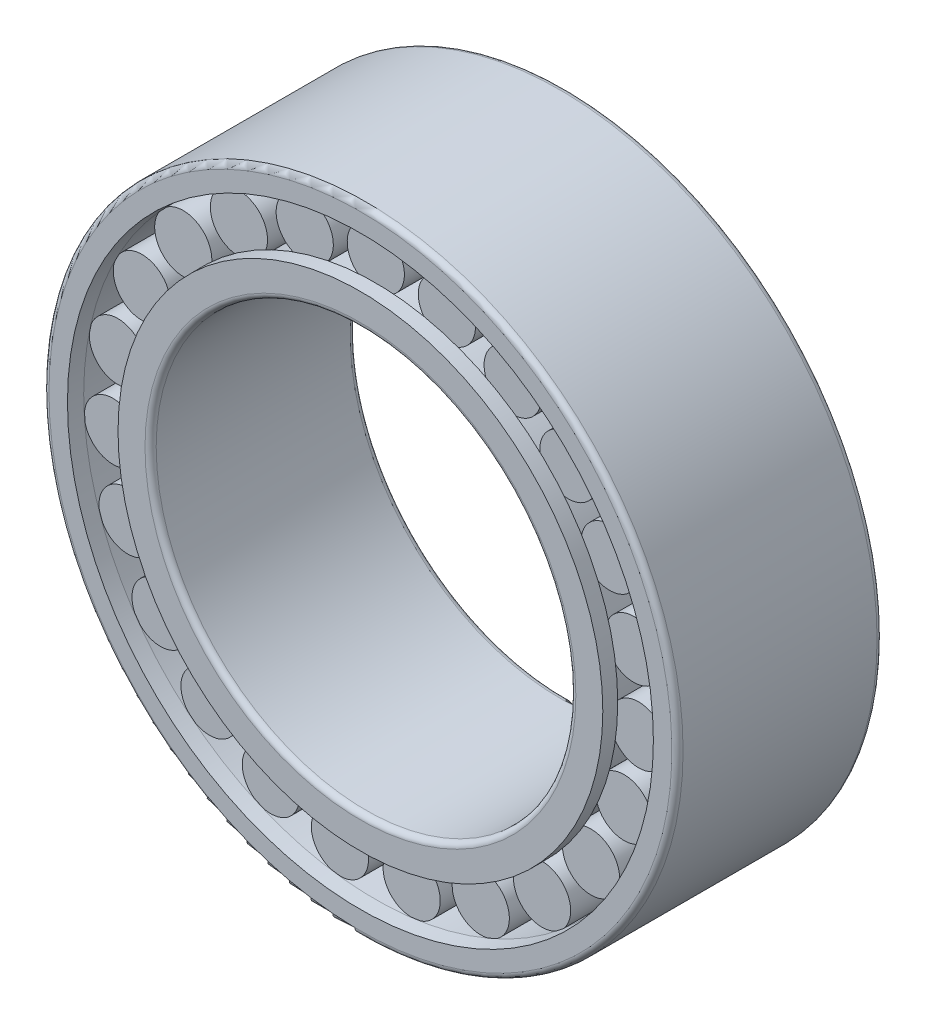
SolidWorks part; units mm, degrees
ref_plane "Front Plane" through (0, 0, 0) normal (0, 0, 1) x (1, 0, 0)
ref_plane "Top Plane" through (0, 0, 0) normal (0, 1, 0) x (1, 0, 0)
ref_plane "Right Plane" through (0, 0, 0) normal (1, 0, 0) x (0, 0, -1)
sketch "BaseSke" plane through (0, 0, 0) normal (1, 0, 0) x (0, 0, -1)
  line L0 (-47.2296, 0) -> (24.6132, 0) construction
  line L1 (-47.2296, 28.25) -> (24.6132, 28.25) construction
  line L2 (0, 129.5214) -> (0, -86.3012) construction
  line L3 (-9.35, 28.25) -> (-9.35, 31.3167) construction
  line L4 (-11, 34) -> (11, 34) construction
  line L5 (-11, 22.5) -> (11, 22.5) construction
  line L6 (-9.35, 25.1833) -> (-1.65, 25.1833)
  line L7 (-9.35, 25.1833) -> (-9.35, 28.25)
  line L8 (-9.35, 28.25) -> (-1.65, 28.25)
  line L9 (-1.65, 25.1833) -> (-1.65, 28.25)
  line L10 (-9.35, 31.3167) -> (-1.65, 31.3167) construction
  line L11 (-1.65, 31.3167) -> (-1.65, 28.25) construction
  dimension "D2" = 7.7
  dimension "D1" = 56.5
  dimension "D3" = 3.0667
  dimension "D4" = 1.65
revolve "Roller" add sketch "BaseSke" angle 360 about L8
sketch "OuterRaceSke" plane through (0, 0, 0) normal (1, 0, 0) x (0, 0, -1)
  line L0 (0, 0) -> (0, 87.5396) construction
  line L1 (-11, 34) -> (11, 34)
  line L2 (-11, 34) -> (-11, 30.508)
  line L3 (-11, 30.508) -> (-9.4, 30.508)
  line L4 (11, 34) -> (11, 30.508)
  line L5 (-50.3916, 0) -> (55.2197, 0) construction
  line L6 (-9.35, 31.3167) -> (-1.65, 31.3167) construction
  line L7 (9.4, 30.508) -> (11, 30.508)
  line L9 (-9.4, 30.508) -> (-9.4, 31.2747)
  line L10 (-9.4, 31.2747) -> (9.4, 31.2747)
  line L11 (9.4, 30.508) -> (9.4, 31.2747)
  dimension "D1" = 18.8
  dimension "D3" = 0.042
  dimension "D2" = 0.7667
revolve "OuterRace" add sketch "OuterRaceSke" angle 360 about L5
mirror "Mirror1" about plane through (0, 0, 0) normal (0, 0, 1) of "Roller"
sketch "InnerRaceSke" plane through (0, 0, 0) normal (1, 0, 0) x (0, 0, -1)
  line L0 (-70.8626, 0) -> (113.5527, 0) construction
  line L1 (0, 58.441) -> (0, -70.8113) construction
  line L2 (-11, 22.5) -> (11, 22.5)
  line L3 (-11, 22.5) -> (-11, 25.992)
  line L4 (-9.4, 25.992) -> (-9.4, 25.2253)
  line L5 (-9.4, 25.992) -> (-11, 25.992)
  line L6 (0, 129.5214) -> (0, -86.3012) construction
  line L7 (-9.4, 25.2253) -> (9.4, 25.2253)
  line L9 (11, 22.5) -> (11, 25.992)
  line L10 (9.4, 25.992) -> (11, 25.992)
  line L11 (9.4, 25.2253) -> (9.4, 25.992)
  line L13 (-9.35, 25.1833) -> (-1.65, 25.1833) construction
  point P17 (0, 22.5)
  dimension "D1" = 18.8
  dimension "D2" = 0.042
  dimension "D3" = 0.7667
revolve "InnerRace" add sketch "InnerRaceSke" angle 360 about L0
sketch "Sketch1" plane through (0, 0, 0) normal (0, 1, 0) x (1, 0, 0)
  line L0 (0, 0) -> (-38.0176, 0) construction
  line L2 (-31.4146, -11) -> (-30.508, -11)
  line L3 (-31.4146, -11) -> (-31.2747, -9.4)
  line L4 (-31.2747, -9.4) -> (-30.508, -9.4)
  line L5 (-30.508, -11) -> (-30.508, -9.4)
  line L11 (-31.4146, 11) -> (-31.2747, 9.4)
  line L12 (-31.2747, 9.4) -> (-30.508, 9.4)
  line L13 (-30.508, 11) -> (-30.508, 9.4)
  line L14 (-31.4146, 11) -> (-30.508, 11)
  line L15 (0, -31.3296) -> (0, 36.1503) construction
  dimension "D1" = 5
revolve "Cut-Revolve1" cut sketch "Sketch1" angle 360 about L15
fillet "Fillet1" radius 0.6 4 edges at (22.5, 0, 11) (34, 0, -11) (34, 0, 11) (22.5, 0, -11)
pattern_circular "CirPatternBall" count 23 over 360 about axis through (0, 0, 50.3916) along (0, 0, -1) of "Roller", "Mirror1"
sketch "SimplifiedSke" plane through (0, 0, 0) normal (1, 0, 0) x (0, 0, -1)
  line L0 (37.5911, 0) -> (-37.5911, 0) construction
  line L1 (-13.1351, 28.25) -> (13.151, 28.25) construction
  line L2 (-9.35, 31.3167) -> (-1.65, 31.3167)
  line L3 (-9.35, 31.3167) -> (-9.35, 25.1833)
  line L4 (-9.35, 25.1833) -> (-1.65, 25.1833)
  line L5 (-1.65, 31.3167) -> (-1.65, 25.1833)
  line L6 (-47.2296, 28.25) -> (24.6132, 28.25) construction
  line L7 (0, 0) -> (0, 50.4947) construction
  line L8 (1.65, 31.3167) -> (1.65, 25.1833)
  line L9 (9.35, 31.3167) -> (1.65, 31.3167)
  line L10 (9.35, 31.3167) -> (9.35, 25.1833)
  line L11 (9.35, 25.1833) -> (1.65, 25.1833)
revolve "Simplified" [suppressed] add sketch "SimplifiedSke" angle 360 about L0
equation "\"D2@BaseSke\" = \"Bearing_Thickness@BaseSke\"*0.35"
equation "\"D1@BaseSke\" =  ( \"Bearing_Inside_Diameter@BaseSke\" + \"Bearing_Outside_Diameter@BaseSke\" )  / 2"
equation "\"D3@BaseSke\" =  ( \"Bearing_Outside_Diameter@BaseSke\" - \"Bearing_Inside_Diameter@BaseSke\" )  / 7.5"
equation "\"D1@OuterRaceSke\" = \"Bearing_Thickness@BaseSke\"*0.85+0.1"
equation "\"D3@OuterRaceSke\" = 0.02+\"Bearing_Thickness@BaseSke\" * 0.001"
equation "\"D2@OuterRaceSke\" = \"D3@BaseSke\" * 0.25"
equation "\"D1@InnerRaceSke\" = \"Bearing_Thickness@BaseSke\"*0.85+0.1"
equation "\"D2@InnerRaceSke\" = \"D3@OuterRaceSke\""
equation "\"D3@InnerRaceSke\" = \"D2@OuterRaceSke\""
equation "\"D1@CirPatternBall\" =  int(  ( \"Bearing_Outside_Diameter@BaseSke\" + \"Bearing_Inside_Diameter@BaseSke\" )  / 2 *  pi  /  ( \"Bearing_Outside_Diameter@BaseSke\" - \"Bearing_Inside_Diameter@BaseSke\" ) * 3 ) "
equation "\"D4@BaseSke\" = \"Bearing_Thickness@BaseSke\" * 0.075"
